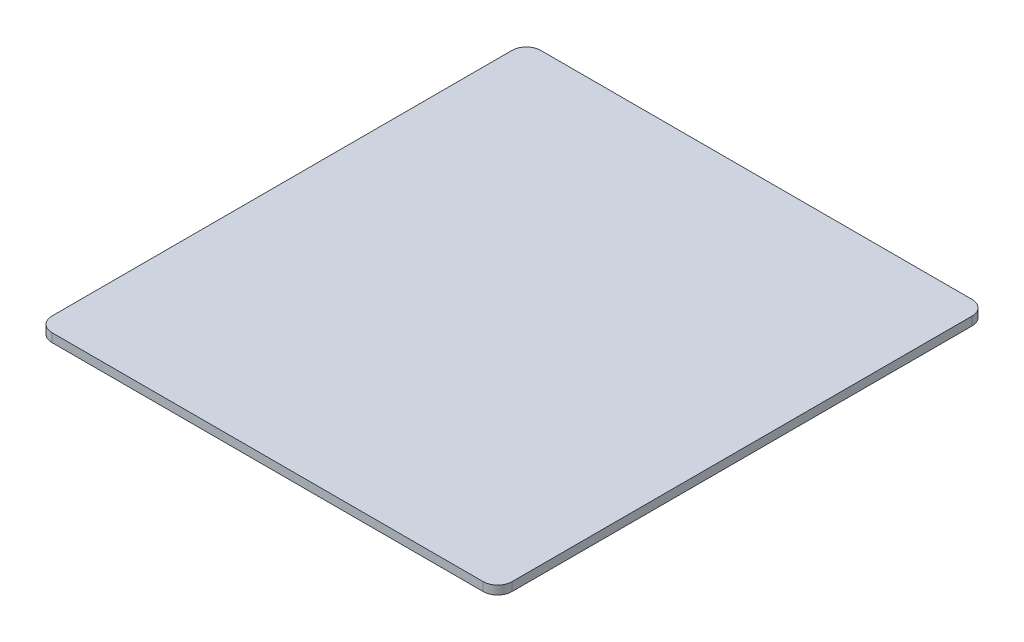
SolidWorks part; units mm, degrees
material "Клен"
ref_plane "Спереди" through (0, 0, 0) normal (0, 0, 1) x (1, 0, 0)
ref_plane "Сверху" through (0, 0, 0) normal (0, 1, 0) x (1, 0, 0)
ref_plane "Справа" through (0, 0, 0) normal (1, 0, 0) x (0, 0, -1)
sketch "Эскиз1" plane through (0, 0, 0) normal (0, 1, 0) x (1, 0, 0)
  line L0 (-199.4521, 0) -> (246.9406, 0) construction
  line L1 (-150, -160) -> (150, -160)
  line L2 (-160, -150) -> (-160, 170)
  line L3 (-150, 180) -> (150, 180)
  line L4 (160, -150) -> (160, 170)
  line L5 (-160, -160) -> (160, 160) construction
  line L6 (-160, 160) -> (160, -160) construction
  line L7 (0, -194.3379) -> (0, 187.7626) construction
  arc A0 (-150, -160) -> (-160, -150) centre (-150, -150) cw
  arc A1 (150, -160) -> (160, -150) centre (150, -150) ccw
  arc A2 (150, 180) -> (160, 170) centre (150, 170) cw
  arc A3 (-160, 170) -> (-150, 180) centre (-150, 170) cw
  point P0 (0, 0)
  dimension "D2" = 10
  dimension "D1" = 320
  dimension "D3" = 340
extrude "Бобышка-Вытянуть1" add sketch "Эскиз1" along normal blind 6
ref_plane "widht" through (0, 0, 0) normal (-1, 0, 0) x (0, 0, 1)
ref_plane "Плоскость2" through (0, 0, -10) normal (0, 0, -1) x (-1, 0, 0)
